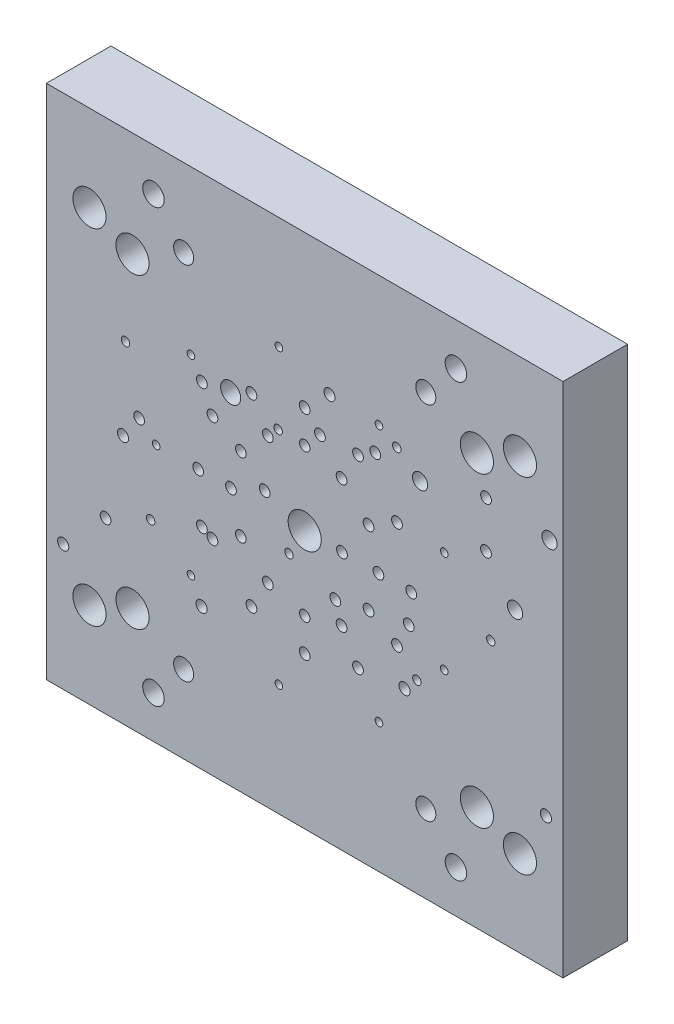
SolidWorks part; units mm, degrees
ref_plane "Front Plane" through (0, 0, 0) normal (0, 0, 1) x (1, 0, 0)
ref_plane "Top Plane" through (0, 0, 0) normal (0, 1, 0) x (1, 0, 0)
ref_plane "Right Plane" through (0, 0, 0) normal (1, 0, 0) x (0, 0, -1)
sketch "Sketch1" plane through (0, 0, 0) normal (0, 0, 1) x (1, 0, 0)
  line L1 (-152.4, 152.4) -> (152.4, 152.4)
  line L2 (-152.4, 152.4) -> (-152.4, -152.4)
  line L3 (-152.4, -152.4) -> (152.4, -152.4)
  line L4 (152.4, 152.4) -> (152.4, -152.4)
  line L5 (-152.4, 152.4) -> (152.4, -152.4) construction
  line L6 (-152.4, -152.4) -> (152.4, 152.4) construction
  point P0 (0, 0)
  dimension "D1" = 304.8
  dimension "D2" = 304.8
extrude "Boss-Extrude1" add sketch "Sketch1" along normal blind 38.1
sketch "Sketch2" plane through (0, 0, 38.1) normal (0, 0, 1) x (1, 0, 0)
  line L0 (-152.4, 0) -> (152.4, 0) construction
  line L5 (-152.4, 152.4) -> (-152.4, -152.4) construction
  line L6 (152.4, -152.4) -> (152.4, 152.4) construction
  line L7 (-152.4, -101.6) -> (152.4, -101.6) construction
  line L8 (-152.4, 101.6) -> (152.4, 101.6) construction
  line L9 (0, 101.6) -> (0, -101.6) construction
  line L10 (127, 101.6) -> (127, -101.6) construction
  line L11 (-127, 101.6) -> (-127, -101.6) construction
  circle A0 centre (-127, 101.6) radius 6.5151
  circle A1 centre (127, 101.6) radius 6.5151
  circle A2 centre (127, -101.6) radius 6.5151
  circle A3 centre (-127, -101.6) radius 6.5151
  circle A4 centre (0, 0) radius 6.5151
  dimension "D5" = 13.0302
  dimension "D1" = 101.6
  dimension "D2" = 101.6
  dimension "D3" = 127
  dimension "D4" = 127
extrude "HAAS T-Slot Holes" cut sketch "Sketch2" against normal through all
sketch "Sketch3" plane through (0, 0, 38.1) normal (0, 0, 1) x (1, 0, 0)
  circle A0 centre (-127, 101.6) radius 9.779
  circle A1 centre (127, 101.6) radius 9.779
  circle A2 centre (0, 0) radius 9.779
  circle A3 centre (127, -101.6) radius 9.779
  circle A4 centre (-127, -101.6) radius 9.779
  dimension "D1" = 19.558
extrude "HAAS Counter Bores" cut sketch "Sketch3" against normal offset from surface (22.225 mm away) 15.875 contours A0 | A1 | A2 | A3 | A4 up to face at (6.5151, 0, 0)
sketch "Sketch4" plane through (0, 0, 38.1) normal (0, 0, 1) x (1, 0, 0)
  line L0 (-127, 90.4875) -> (127, 90.4875) construction
  line L1 (-127, 30.1625) -> (127, 30.1625) construction
  line L2 (-127, 30.1625) -> (-127, -30.1625) construction
  line L3 (-127, -30.1625) -> (127, -30.1625) construction
  line L4 (127, 30.1625) -> (127, -30.1625) construction
  line L5 (-127, 30.1625) -> (127, -30.1625) construction
  line L6 (-127, -30.1625) -> (127, 30.1625) construction
  line L7 (-127, -90.4875) -> (127, -90.4875) construction
  line L8 (-101.6, 90.4875) -> (-101.6, 84.1375) construction
  line L9 (-101.6, -90.4875) -> (-101.6, -84.1375) construction
  line L10 (101.6, -90.4875) -> (101.6, -84.1375) construction
  line L11 (101.6, 90.4875) -> (101.6, 84.1375) construction
  circle A0 centre (-101.6, 90.4875) radius 6.5151
  circle A1 centre (101.6, 90.4875) radius 6.5151
  circle A2 centre (-101.6, -90.4875) radius 6.5151
  circle A3 centre (101.6, -90.4875) radius 6.5151
  point P0 (0, 0)
  dimension "D9" = 13.0302
  dimension "D1" = 60.325
  dimension "D2" = 254
  dimension "D5" = 203.2
  dimension "D6" = 25.4
  dimension "D7" = 203.2
  dimension "D8" = 6.35
  dimension "D3" = 60.325
  dimension "D4" = 60.325
extrude "Tormach T-Slot Holes" cut sketch "Sketch4" against normal through all
sketch "Sketch5" plane through (0, 0, 38.1) normal (0, 0, 1) x (1, 0, 0)
  circle A0 centre (-101.6, 90.4875) radius 9.779
  circle A1 centre (101.6, 90.4875) radius 9.779
  circle A2 centre (101.6, -90.4875) radius 9.779
  circle A3 centre (-101.6, -90.4875) radius 9.779
  dimension "D1" = 19.558
extrude "Tormach Counter bores" cut sketch "Sketch5" against normal up to surface (22.225 mm away) up to face at (-117.221, 101.6, 15.875)
sketch "Sketch6" plane through (0, 0, 38.1) normal (0, 0, 1) x (1, 0, 0)
  circle A0 centre (0, 0) radius 43.5 construction
  circle A1 centre (0, 43.5) radius 3.0734
  circle A2 centre (0, -43.5) radius 3.0734
  dimension "D1" = 87.0001
  dimension "D2" = 6.1468
extrude "Sprocket Locating Holes" cut sketch "Sketch6" against normal blind 6.35
sketch "Sketch7" plane through (0, 0, 38.1) normal (0, 0, 1) x (1, 0, 0)
  circle A0 centre (0, 0) radius 43.5 construction
  circle A2 centre (43.5, 0) radius 3.175
  circle A4 centre (37.6721, -21.75) radius 3.175
  circle A5 centre (21.75, -37.6721) radius 3.175
  circle A6 centre (0, -43.5) radius 3.175 [skipped]
  circle A7 centre (-21.75, -37.6721) radius 3.175
  circle A8 centre (-37.6721, -21.75) radius 3.175
  circle A9 centre (-43.5, 0) radius 3.175
  circle A10 centre (-37.6721, 21.75) radius 3.175
  circle A11 centre (-21.75, 37.6721) radius 3.175
  circle A12 centre (0, 43.5) radius 3.175 [skipped]
  circle A13 centre (21.75, 37.6721) radius 3.175
  circle A14 centre (37.6721, 21.75) radius 3.175
  point P31 (0, 0)
  dimension "D1" = 87.0001
  dimension "D2" = 6.35
  dimension "D3" = 12
extrude "Sprocket Mounting clearance holes" cut sketch "Sketch7" against normal blind 9.525
sketch "Sketch8" plane through (0, 0, 38.1) normal (0, 0, 1) x (1, 0, 0)
  line L1 (-71.4375, 106.4641) -> (71.4375, 106.4641) construction
  line L2 (-71.4375, 106.4641) -> (-71.4375, -106.4641) construction
  line L3 (-71.4375, -106.4641) -> (71.4375, -106.4641) construction
  line L4 (71.4375, 106.4641) -> (71.4375, -106.4641) construction
  line L5 (-71.4375, 106.4641) -> (71.4375, -106.4641) construction
  line L6 (-71.4375, -106.4641) -> (71.4375, 106.4641) construction
  circle A0 centre (-71.4375, 106.4641) radius 5.9182
  circle A1 centre (71.4375, 106.4641) radius 5.9182
  circle A2 centre (71.4375, -106.4641) radius 5.9182
  circle A3 centre (-71.4375, -106.4641) radius 5.9182
  point P0 (0, 0)
  dimension "D3" = 11.8364
  dimension "D1" = 142.875
  dimension "D2" = 212.9282
extrude "1/2-13 Tapped Holes" cut sketch "Sketch8" against normal blind 19.05
sketch "Sketch9" plane through (0, 0, 38.1) normal (0, 0, 1) x (1, 0, 0)
  circle A0 centre (-117.5189, -52.2876) radius 3.175
  circle A1 centre (-60.6634, -28.4101) radius 3.175
  circle A2 centre (-60.6634, 45.677) radius 3.175
  circle A3 centre (-23.6198, 8.6335) radius 3.175
  circle A4 centre (-97.707, 8.6335) radius 3.175
  circle A5 centre (18.0623, -26.1797) radius 3.175
  circle A6 centre (21.9762, 0) radius 3.175
  circle A7 centre (61.3833, -17.3739) radius 3.175
  circle A8 centre (106.976, 70.3959) radius 3.175
  circle A9 centre (106.976, 42.9004) radius 3.175
  circle A10 centre (144.4539, 67.4373) radius 4.5
  circle A11 centre (124.1092, 21.6131) radius 4.5
  circle A12 centre (68.0681, 59.3279) radius 4.5
  circle A13 centre (58.9353, -51.2652) radius 3.3
  circle A14 centre (-142.4923, -78.095) radius 3.3
  circle A15 centre (-105.7351, 43.7713) radius 2.5
  circle A16 centre (-90.8975, -39.8642) radius 2.5
  circle A17 centre (-9.2711, -16.3656) radius 2.5
  circle A18 centre (-15.6655, 43.8657) radius 2.5
  circle A20 centre (14.6267, 76.8405) radius 3.3
  circle A21 centre (8.9855, 53.4682) radius 3.175
  circle A22 centre (41.6559, 60.6579) radius 3.175
extrude "SSB Holes" cut sketch "Sketch9" against normal blind 19.05
ref_axis "Axis1" through (0, 0, 0) along (0, 0, 1)
sketch "Sketch10" plane through (0, 0, 38.1) normal (0, 0, 1) x (1, 0, 0)
  circle A0 centre (0, 0) radius 62.865 construction
  circle A1 centre (0, 62.865) radius 3.175
  circle A13 centre (31.4325, 54.4427) radius 3.175
  circle A14 centre (54.4427, 31.4325) radius 3.175
  circle A15 centre (62.865, 0) radius 3.175
  circle A16 centre (54.4427, -31.4325) radius 3.175
  circle A17 centre (31.4325, -54.4427) radius 3.175
  circle A18 centre (0, -62.865) radius 3.175
  circle A19 centre (-31.4325, -54.4427) radius 3.175
  circle A20 centre (-54.4427, -31.4325) radius 3.175
  circle A21 centre (-62.865, 0) radius 3.175
  circle A22 centre (-54.4427, 31.4325) radius 3.175
  circle A23 centre (-31.4325, 54.4427) radius 3.175
  point P30 (0, 0)
  point P56 (0, 0)
  dimension "D1" = 125.73
  dimension "D2" = 6.35
  dimension "D4" = 12
extrude "Sprocket Countersunk Holes" cut sketch "Sketch10" against normal blind 19.05
sketch "Sketch12" plane through (0, 0, 38.1) normal (0, 0, 1) x (1, 0, 0)
  circle A0 centre (-107.2144, -4.9977) radius 3.3
  circle A1 centre (-60.8212, -69.1392) radius 3.3
  circle A2 centre (142.3129, -74.567) radius 3.3
  circle A4 centre (54.3307, 69.7186) radius 2.4964
  circle A5 centre (109.7823, -1.2607) radius 2.5
  circle A6 centre (66.2094, -43.3332) radius 2.5
  circle A7 centre (-43.6886, 48.7489) radius 5.9182
  circle A8 centre (-71.4375, 106.4641) radius 5.9182 construction
extrude "DSB Holes" cut sketch "Sketch12" against normal blind 19.05
sketch "Brake Rotor Toe Clamp Holes" plane through (0, 0, 38.1) normal (0, 0, 1) x (1, 0, 0)
  line L0 (-74.6653, 106.6331) -> (74.6653, -106.6331) construction
  line L1 (74.6653, 106.6331) -> (-74.6653, -106.6331) construction
  line L2 (-74.6653, 106.6331) -> (-89.2342, 127.4396) construction
  line L3 (74.6653, 106.6331) -> (89.2342, 127.4396) construction
  line L4 (-74.6653, -106.6331) -> (-89.2342, -127.4396) construction
  line L5 (74.6653, -106.6331) -> (89.2342, -127.4396) construction
  line L6 (0, 0) -> (192.0367, 0) construction
  line L7 (0, 0) -> (-160.9096, 0) construction
  line L8 (0, 0) -> (0, 219.8313) construction
  line L9 (0, 0) -> (-215.8918, 38.0675) construction
  circle A0 centre (0, 0) radius 130.175 construction
  circle A6 centre (-89.2342, 127.4396) radius 6.35
  circle A7 centre (89.2342, 127.4396) radius 6.35
  circle A8 centre (89.2342, -127.4396) radius 6.35
  circle A9 centre (-89.2342, -127.4396) radius 6.35
  circle A10 centre (-87.63, 0) radius 2.3813 construction
  circle A12 centre (-74.93, 0) radius 2.3813 construction
  circle A13 centre (-80.0452, 14.1141) radius 2.3813
  circle A14 centre (-70.4112, 25.6276) radius 2.3812 construction
  circle A15 centre (-70.3905, 40.64) radius 2.3812 construction
  circle A16 centre (-82.3453, 29.9712) radius 2.3812 construction
  circle A17 centre (-57.3997, 48.1641) radius 2.3813 construction
  circle A18 centre (-52.2458, 62.2641) radius 2.3812
  circle A19 centre (-67.1285, 56.3275) radius 2.3812 construction
  circle A20 centre (-37.465, 64.8913) radius 2.3813 construction
  circle A21 centre (-27.7994, 76.3782) radius 2.3813 construction
  circle A22 centre (-43.815, 75.8898) radius 2.3813 construction
  circle A23 centre (-13.0115, 73.7916) radius 2.3813 construction
  circle A24 centre (0, 81.28) radius 2.3813
  circle A25 centre (-15.2168, 86.2987) radius 2.3813 construction
  circle A26 centre (13.0115, 73.7916) radius 2.3812 construction
  circle A27 centre (27.7994, 76.3782) radius 2.3812 construction
  circle A28 centre (15.2168, 86.2987) radius 2.3813 construction
  circle A29 centre (37.465, 64.8913) radius 2.3812 construction
  circle A30 centre (52.2458, 62.2641) radius 2.3813
  circle A31 centre (43.815, 75.8898) radius 2.3812 construction
  circle A32 centre (57.3997, 48.1641) radius 2.3813 construction
  circle A33 centre (70.3905, 40.64) radius 2.3813 construction
  circle A34 centre (67.1285, 56.3275) radius 2.3813 construction
  circle A35 centre (70.4112, 25.6276) radius 2.3813 construction
  circle A36 centre (80.0452, 14.1141) radius 2.3813
  circle A37 centre (82.3453, 29.9712) radius 2.3813 construction
  circle A38 centre (74.93, 0) radius 2.3813 construction
  circle A39 centre (80.0452, -14.1141) radius 2.3813 construction
  circle A40 centre (87.63, 0) radius 2.3813 construction
  circle A41 centre (70.4112, -25.6276) radius 2.3812 construction
  circle A42 centre (70.3905, -40.64) radius 2.3813
  circle A43 centre (82.3453, -29.9712) radius 2.3812 construction
  circle A44 centre (57.3997, -48.1641) radius 2.3813 construction
  circle A45 centre (52.2458, -62.2641) radius 2.3813 construction
  circle A46 centre (67.1285, -56.3275) radius 2.3812 construction
  circle A47 centre (37.465, -64.8913) radius 2.3813 construction
  circle A48 centre (27.7994, -76.3782) radius 2.3813
  circle A49 centre (43.815, -75.8898) radius 2.3813 construction
  circle A50 centre (13.0115, -73.7916) radius 2.3813 construction
  circle A51 centre (0, -81.28) radius 2.3812 construction
  circle A52 centre (15.2168, -86.2987) radius 2.3813 construction
  circle A53 centre (-13.0115, -73.7916) radius 2.3813 construction
  circle A54 centre (-27.7994, -76.3782) radius 2.3813
  circle A55 centre (-15.2168, -86.2987) radius 2.3813 construction
  circle A56 centre (-37.465, -64.8913) radius 2.3813 construction
  circle A57 centre (-52.2458, -62.2641) radius 2.3813 construction
  circle A58 centre (-43.815, -75.8898) radius 2.3812 construction
  circle A59 centre (-57.3997, -48.1641) radius 2.3813 construction
  circle A60 centre (-70.3905, -40.64) radius 2.3813
  circle A61 centre (-67.1285, -56.3275) radius 2.3813 construction
  circle A62 centre (-70.4112, -25.6276) radius 2.3813 construction
  circle A63 centre (-80.0452, -14.1141) radius 2.3813 construction
  circle A64 centre (-82.3453, -29.9712) radius 2.3813 construction
  point P27 (0, 0)
  point P130 (0, 0)
  dimension "D1" = 260.35
  dimension "D2" = 12.7
  dimension "D3" = 12.7
  dimension "D4" = 12.7
  dimension "D5" = 12.7
  dimension "D17" = 4.7625
  dimension "D18" = 81.28
  dimension "D19" = 18
  dimension "D14" = 4.7625
  dimension "D15" = 4.7625
  dimension "D6" = 25.4
  dimension "D7" = 25.4
  dimension "D8" = 25.4
  dimension "D9" = 25.4
  dimension "D10" = 55
  dimension "D11" = 55
  dimension "D12" = 87.63
  dimension "D13" = 12.7
  dimension "D16" = 10
hole_wizard "Rotor Clamp Bolts" positions "Sketch15" profile "Sketch16" hole size "M4" standard "AS"
sketch "Sketch15" plane through (0, 0, 38.1) normal (0, 0, 1) x (1, 0, 0)
  point P0 (-87.63, 0)
  point P3 (-67.1285, -56.3275)
  point P6 (-15.2168, -86.2987)
  point P9 (43.815, -75.8898)
  point P12 (82.3453, -29.9712)
  point P15 (82.3453, 29.9712)
  point P18 (43.815, 75.8898)
  point P21 (-15.2168, 86.2987)
  point P24 (-67.1285, 56.3275)
sketch "Sketch16" plane through (-87.63, 0, 38.1) normal (1, 0, 0) x (0, -1, 0)
  line L0 (0, 0) -> (0, 20.4019)
  line L1 (0, 20.4019) -> (2.25, 19.05)
  line L2 (2.25, 19.05) -> (2.25, 0)
  line L5 (2.25, 0) -> (0, 0)
  line L10 (0, 20.4019) -> (-2.25, 19.05) construction
  line L11 (0, -6.35) -> (0, 107.95) construction
  dimension "Hole Dia." = 4.5
  dimension "Hole Depth" = 19.05
  dimension "Drill Angle" = 118
extrude "Outer Toe Clamp" cut sketch "Brake Rotor Toe Clamp Holes" against normal blind 19.05 contours A8 | A9 | A7 | A6
equation "\"boltRotor\"=0.75"
equation "\"bolt\"=0.51159"
